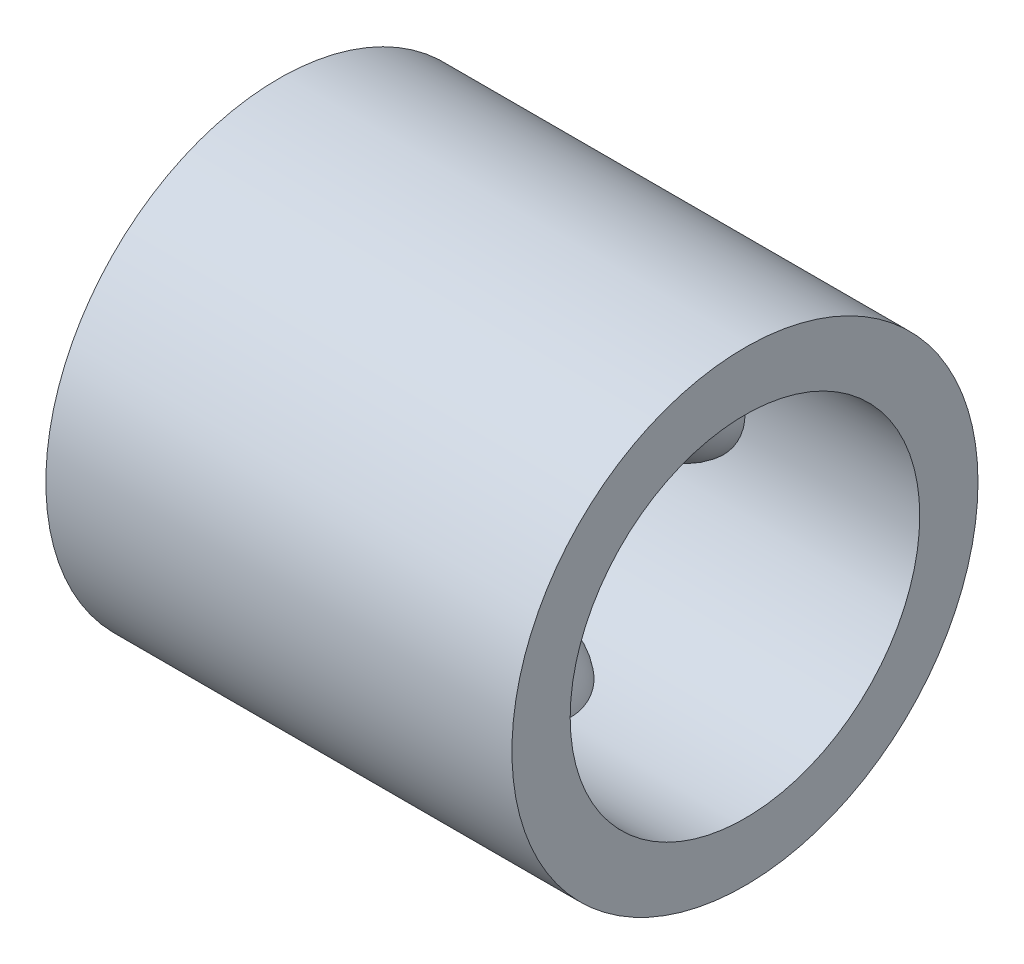
SolidWorks part; units mm, degrees
ref_plane "Front Plane" through (0, 0, 0) normal (0, 0, 1) x (1, 0, 0)
ref_plane "Top Plane" through (0, 0, 0) normal (0, 1, 0) x (1, 0, 0)
ref_plane "Right Plane" through (0, 0, 0) normal (1, 0, 0) x (0, 0, -1)
sketch "Sketch2" plane through (0, 0, 0) normal (1, 0, 0) x (0, 0, -1)
  line L0 (0, 0) -> (0, 3.2449) construction
  line L1 (0, 0) -> (0, -3.5059) construction
  line L2 (0, 0) -> (-3.0497, 0) construction
  line L3 (0, 0) -> (3.0497, 0) construction
  circle A0 centre (0, 0) radius 2.25
  circle A1 centre (0, 0) radius 3
extrude "Boss-Extrude1" add sketch "Sketch2" along normal mid plane 6
sketch "Sketch8" plane through (0, 0, 0) normal (1, 0, 0) x (0, 0, -1)
  line L0 (-0.0003, -0.0367) -> (-2.25, 0) construction
  line L1 (-2.25, 0) -> (-2.2377, 0.7509)
  line L2 (-2.25, 0) -> (-1.5001, -0.0122)
  line L3 (-2.9999, 0.0122) -> (-3.4122, 0.019) construction
  arc A0 (-1.5001, -0.0122) -> (-2.2377, 0.7509) centre (-2.25, 0.001) ccw
  point P7 (0, 0)
  point P8 (0, 0)
  point P10 (0, 0)
  point P11 (0, 0)
  point P12 (0, 0)
  point P14 (0, 0)
  point P15 (0, 0)
revolve "Revolve18" add sketch "Sketch8" angle 360 about L2
sketch "Sketch10" plane through (0, 0, 0) normal (1, 0, 0) x (0, 0, -1)
  line L0 (0, 0) -> (2.25, 0) construction
  line L1 (2.25, 0) -> (2.25, 0.75)
  line L2 (2.25, 0) -> (1.5, 0)
  line L3 (2.9999, 0) -> (3.2226, 0) construction
  arc A0 (2.25, 0.75) -> (1.5, 0) centre (2.25, 0) ccw
  point P2 (0, 0)
  point P3 (0, 0)
  point P6 (0, 0)
  point P7 (0, 0)
  point P9 (0, 0)
  point P10 (0, 0)
  point P12 (0, 0)
  point P13 (0, 0)
  point P14 (0, 0)
  point P15 (0, 0)
revolve "Revolve19" add sketch "Sketch10" angle 360 about L2
sketch "Sketch11" plane through (0, 0, 0) normal (1, 0, 0) x (0, 0, -1)
  line L0 (0, 0) -> (0, 2.25) construction
  line L1 (0.0011, 2.25) -> (-0.75, 2.2511)
  line L2 (0.0011, 2.25) -> (0, 1.5)
  line L3 (0, 3) -> (0, 3.8827) construction
  arc A0 (-0.75, 2.2511) -> (0, 1.5) centre (0, 2.25) ccw
  point P6 (0, 0)
  point P7 (0, 0)
revolve "Revolve20" add sketch "Sketch11" angle 360 about L2
sketch "Sketch13" plane through (0, 0, 0) normal (1, 0, 0) x (0, 0, -1)
  line L0 (0, 0) -> (0, -2.25) construction
  line L1 (0, -1.5) -> (0, -2.25)
  line L2 (0, -2.25) -> (0.75, -2.25)
  line L3 (0, -3) -> (0, -4.4497) construction
  arc A0 (0.75, -2.25) -> (0, -1.5) centre (0, -2.25) ccw
  point P6 (0, 0)
revolve "Revolve21" add sketch "Sketch13" angle 360 about L1
